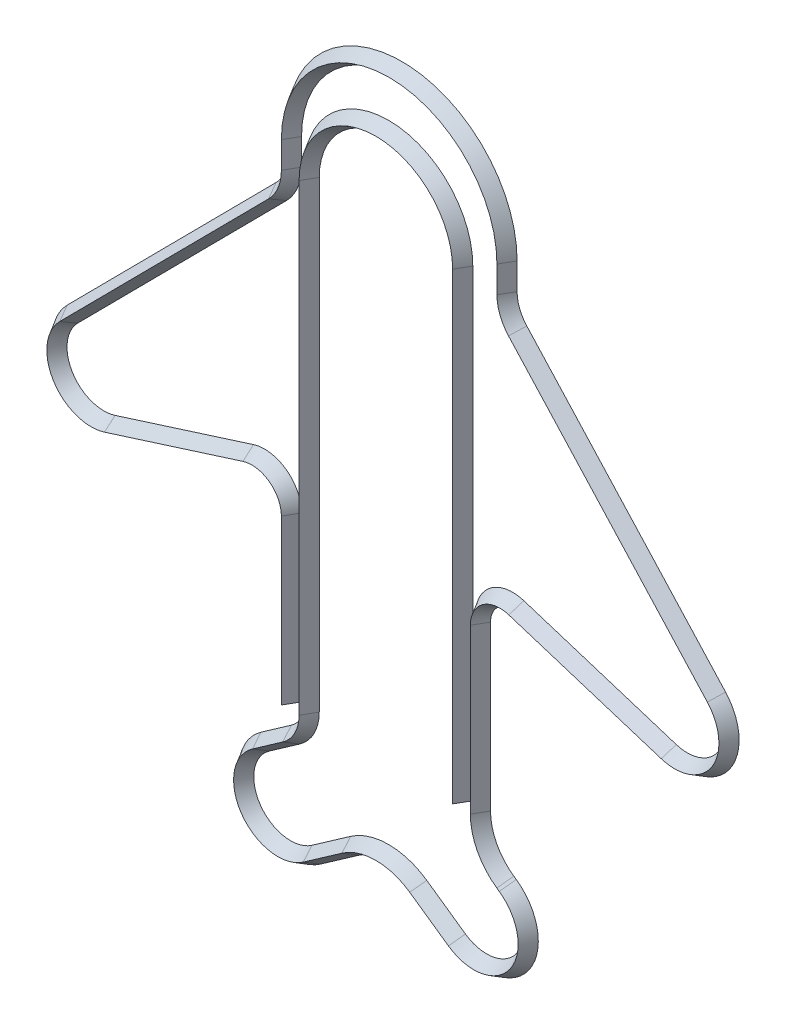
SolidWorks part; units mm, degrees
ref_plane "Спереди" through (0, 0, 0) normal (0, 0, 1) x (1, 0, 0)
ref_plane "Сверху" through (0, 0, 0) normal (0, 1, 0) x (1, 0, 0)
ref_plane "Справа" through (0, 0, 0) normal (1, 0, 0) x (0, 0, -1)
sketch "Эскиз1" plane through (0, 0, 0) normal (0, 0, 1) x (1, 0, 0)
  line L0 (11.4715, -8.0325) -> (24.5746, -17.2073)
  line L1 (41.7819, 7.3673) -> (40.9549, 7.9463)
  line L2 (32, 25.1485) -> (32, 80.5541)
  line L3 (45.0232, 90.0862) -> (96.6387, 73.7159)
  line L4 (112.2498, 98.1292) -> (44.9237, 171.8524)
  line L5 (0, 0) -> (0, 116.4649) construction
  line L6 (-107.0725, 100.083) -> (-36.3488, 171.4058)
  line L7 (-45.0232, 90.0862) -> (-91.8866, 75.2231)
  line L8 (-41.7819, 7.3673) -> (-31.5134, 14.5573)
  line L9 (-26, 25.1485) -> (-26, 181.9675)
  line L10 (-11.4715, -8.0325) -> (-24.5746, -17.2073)
  line L11 (-32, 80.5541) -> (-32, 25.1485)
  line L12 (26, 181.9675) -> (26, 25.1485)
  line L13 (-32, 181.9675) -> (-32, 190.9675)
  line L14 (41, 181.9675) -> (41, 190.9675)
  arc A0 (24.5746, -17.2073) -> (41.7819, 7.3673) centre (33.1782, -4.92) ccw
  arc A1 (-24.5746, -17.2073) -> (-41.7819, 7.3673) centre (-33.1782, -4.92) cw
  arc A2 (-32, 190.9675) -> (41, 190.9675) centre (4.5, 190.9675) cw
  arc A3 (-26, 181.9675) -> (26, 181.9675) centre (0, 181.9675) cw
  arc A4 (11.4715, -8.0325) -> (-11.4715, -8.0325) centre (0, -24.4155) ccw
  arc A5 (-31.5134, 14.5573) -> (-26, 25.1485) centre (-38.9295, 25.1485) ccw
  arc A6 (40.9549, 7.9463) -> (32, 25.1485) centre (53, 25.1485) cw
  arc A7 (-32, 80.5541) -> (-45.0232, 90.0862) centre (-42, 80.5541) ccw
  arc A8 (32, 80.5541) -> (45.0232, 90.0862) centre (42, 80.5541) cw
  arc A9 (96.6387, 73.7159) -> (112.2498, 98.1292) centre (101.1735, 88.014) ccw
  arc A10 (-91.8866, 75.2231) -> (-107.0725, 100.083) centre (-96.4213, 89.5212) cw
  arc A11 (44.9237, 171.8524) -> (41, 181.9675) centre (56, 181.9675) cw
  arc A12 (-32, 181.9675) -> (-36.3488, 171.4058) centre (-47, 181.9675) cw
  point P9 (0, 0)
  point P16 (42, 175.1485)
  point P29 (0, 0)
  point P35 (32, 14.2166)
  point P38 (-32, 94.2166)
  point P41 (32, 94.2166)
  point P44 (150, 56.792)
  point P47 (-150, 56.792)
  dimension "D1" = 30
  dimension "D3" = 15
  dimension "D10" = 6
  dimension "D13" = 20
  dimension "D14" = 15
  dimension "D15" = 21
  dimension "D16" = 10
  dimension "D17" = 10
  dimension "D18" = 15
  dimension "D12" = 6
  dimension "D2" = 55
  dimension "D4" = 32
  dimension "D5" = 30
  dimension "D6" = 42
  dimension "D7" = 80
  dimension "D8" = 150
  dimension "D9" = 150
  dimension "D19" = 9
  dimension "D21" = 15
  dimension "D22" = 190
ref_plane "Плоскость4" through (0, 25.1485, 0) normal (0, 1, 0) x (1, 0, 0)
sketch "Эскиз2" plane through (0, 25.1485, 0) normal (0, 1, 0) x (1, 0, 0)
  line L1 (26, -2.8868) -> (28.5, 1.4434)
  line L2 (28.5, 1.4434) -> (23.5, 1.4434)
  line L3 (23.5, 1.4434) -> (26, -2.8868)
  circle A0 centre (26, 0) radius 1.4434 construction
  dimension "D1" = 5
sweep "По траектории1" add profiles "Эскиз2" path "Эскиз1"
